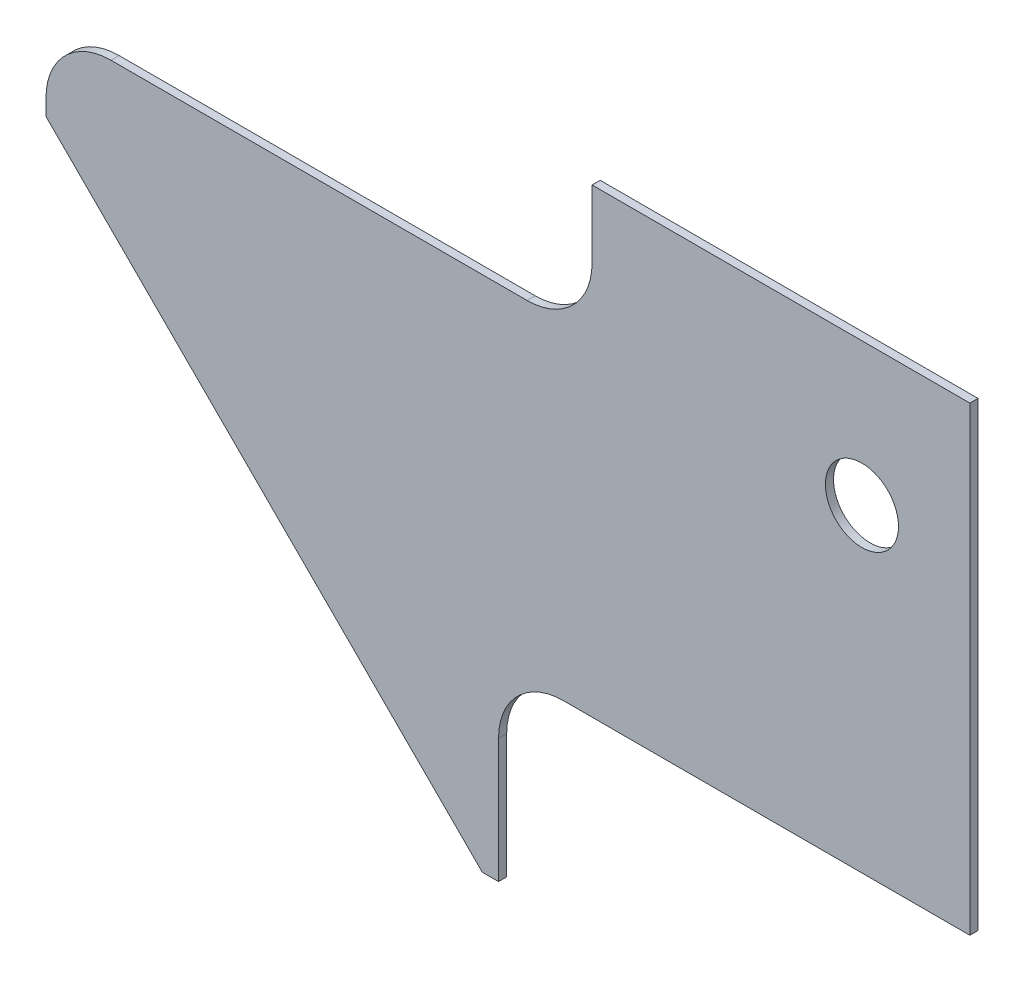
SolidWorks part; units mm, degrees
ref_plane "Front Plane" through (0, 0, 0) normal (0, 0, 1) x (1, 0, 0)
ref_plane "Top Plane" through (0, 0, 0) normal (0, 1, 0) x (1, 0, 0)
ref_plane "Right Plane" through (0, 0, 0) normal (1, 0, 0) x (0, 0, -1)
sketch "Sketch1" plane through (0, 0, 0) normal (0, 0, 1) x (1, 0, 0)
  line L0 (-138.2594, 48.9915) -> (32.2106, -121.4785)
  line L1 (32.2106, -121.4785) -> (222.7106, -121.4785)
  line L2 (-138.2594, 145.2215) -> (-138.2594, 48.9915)
  line L3 (-138.2594, 145.2215) -> (222.7106, 145.2215)
  line L4 (222.7106, -121.4785) -> (222.7106, 145.2215)
  circle A0 centre (180.538, 76.832) radius 14.2875
  circle A2 centre (180.538, 76.832) radius 64.9605 construction
  circle A3 centre (180.538, 76.832) radius 318.7974 construction
  point P0 (0, 0)
  point P2 (180.538, 76.832)
  dimension "D4" = 198.3105
  dimension "D1" = 45
  dimension "D2" = 266.7
  dimension "D5" = 245.11
extrude "Boss-Extrude1" add sketch "Sketch1" along normal blind 3.175
sketch "Sketch2" plane through (0, 0, 3.175) normal (0, 0, 1) x (1, 0, 0)
  line L0 (32.2106, -121.4785) -> (222.7106, -121.4785) construction
  line L1 (222.7634, -121.4785) -> (38.5606, -121.4785)
  line L2 (222.7634, -121.4785) -> (222.7634, -47.5645)
  line L3 (222.7634, -47.5645) -> (38.5606, -47.5645)
  line L4 (38.5606, -121.4785) -> (38.5606, -47.5645)
extrude "Cut-Extrude1" cut sketch "Sketch2" against normal through all contours L3 L4 L1 L2
fillet "Fillet1" radius 25.4 1 edges at (38.5606, -47.5645, 1.5875)
sketch "Sketch4" plane through (0, 0, 3.175) normal (0, 0, 1) x (1, 0, 0)
  line L1 (-138.2594, 145.2215) -> (-138.2594, 48.9915) construction
  line L3 (-138.2594, 145.2215) -> (75.1006, 145.2215)
  line L4 (-138.2594, 145.2215) -> (-138.2594, 80.7415)
  line L5 (-138.2594, 80.7415) -> (75.1006, 80.7415)
  line L6 (75.1006, 145.2215) -> (75.1006, 80.7415)
extrude "Cut-Extrude2" cut sketch "Sketch4" against normal through all contours L5 L6 L3 L4
fillet "Fillet2" radius 25.4 2 edges at (-138.2594, 80.7415, 1.5875) (75.1006, 80.7415, 1.5875)
sketch "Sketch7" plane through (0, 0, 3.175) normal (0, 0, 1) x (1, 0, 0)
  line L0 (222.7106, -47.5645) -> (222.7106, 145.2215) construction
  line L1 (75.1006, 145.2215) -> (222.7106, 145.2215)
  line L2 (75.1006, 145.2215) -> (75.1006, 132.5215)
  line L3 (75.1006, 132.5215) -> (222.7106, 132.5215)
  line L4 (222.7106, 145.2215) -> (222.7106, 132.5215)
  dimension "D1" = 12.7
extrude "Cut-Extrude4" cut sketch "Sketch7" against normal through all
